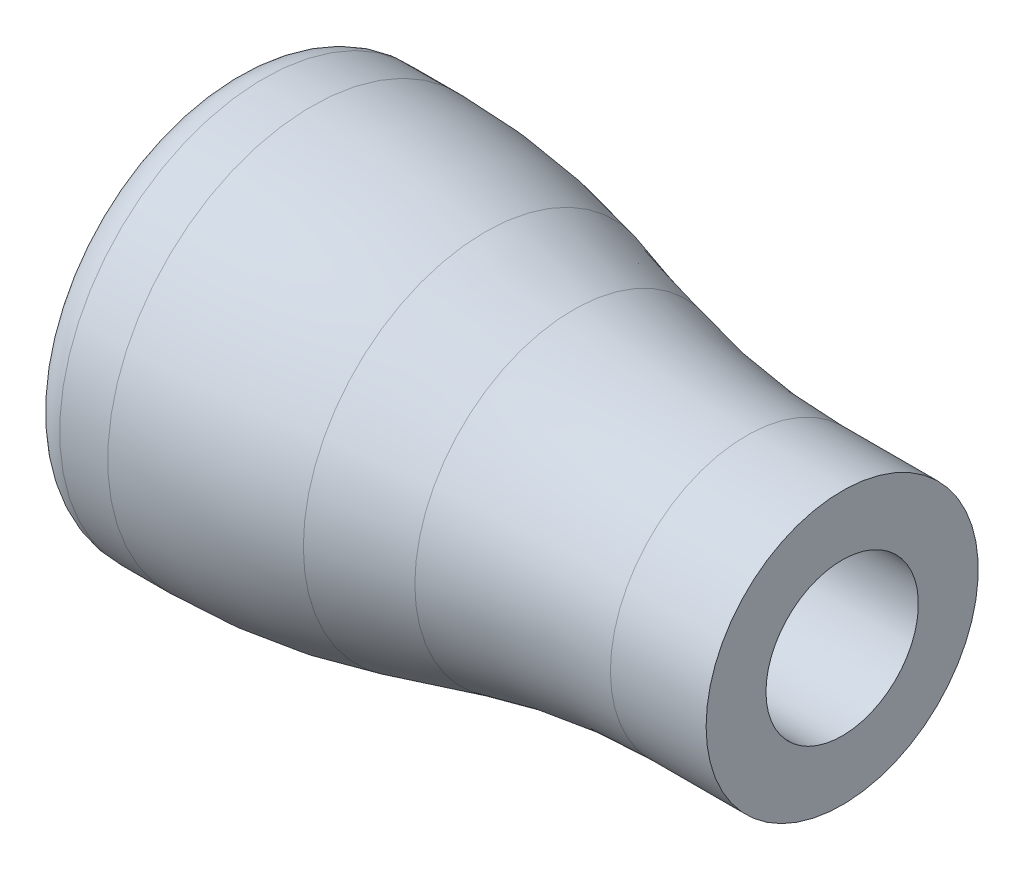
SolidWorks part; units mm, degrees
ref_plane "Front Plane" through (0, 0, 0) normal (0, 0, 1) x (1, 0, 0)
ref_plane "Top Plane" through (0, 0, 0) normal (0, 1, 0) x (1, 0, 0)
ref_plane "Right Plane" through (0, 0, 0) normal (1, 0, 0) x (0, 0, -1)
sketch "Sketch1" plane through (0, 0, 0) normal (0, 0, 1) x (1, 0, 0)
  line L0 (-11.0024, 0) -> (5.8653, 0) construction
  line L1 (-9, 0) -> (-9, 2.03)
  line L2 (-9, 2.03) -> (-8.95, 2.03)
  line L3 (-8.95, 2.03) -> (-8.95, 2.08)
  line L4 (-9, 0) -> (0, 0)
  line L5 (-8.95, 2.08) -> (-6.9, 2.08)
  line L6 (-6.9, 2.08) -> (-6.9, 0.3262)
  line L7 (-6.9, 0.3262) -> (-2.3, 0.3262)
  line L8 (-2.3, 0.3262) -> (-2.3, 1.12)
  line L9 (-2.3, 1.12) -> (0, 1.12)
  line L10 (0, 1.12) -> (0, 0)
  point P5 (0, 0)
  point P8 (-11.0024, 0)
  point P15 (-5.2139, 1.1723)
  point P16 (-8.95, 2.055)
  dimension "D1" = 1.12
  dimension "D2" = 2.3
  dimension "D3" = 2.05
  dimension "D4" = 0.05
  dimension "D5" = 0.05
  dimension "D6" = 2.03
  dimension "D7" = 9
  dimension "D8" = 1.7538
  dimension "D9" = 2.05
  dimension "D10" = 0.3262
sketch "Sketch2" plane through (0, 0, 0) normal (0, 0, 1) x (1, 0, 0)
  line L0 (-11.0024, 0) -> (5.8653, 0) construction
  line L1 (-9, 0) -> (-9, 3)
  line L2 (-9, 3) -> (-6.5, 3)
  line L3 (-6.5, 3) -> (-2.7, 2)
  line L4 (-2.7, 2) -> (0, 2)
  line L5 (0, 2) -> (0, 0)
  line L6 (-9, 0) -> (0, 0)
  point P6 (-2.7981, 1.9383)
  dimension "D1" = 3
  dimension "D2" = 9
  dimension "D3" = 2
  dimension "D4" = 2.7
  dimension "D5" = 2.5
revolve "Revolve1" add sketch "Sketch2" angle 360 about L0
revolve "Cut-Revolve1" cut sketch "Sketch1" angle 360 about L0
fillet "Fillet2" radius 0.05 1 edges at (-8.95, 0, 2.03)
fillet "Fillet4" radius 0.02 1 edges at (-9, 0, 2.03)
fillet "Fillet5" radius 10 1 edges at (-6.5, 0, 3)
fillet "Fillet6" radius 10 1 edges at (-2.7, 0, 2)
fillet "Fillet7" radius 0.5 1 edges at (-9, 0, 3)
